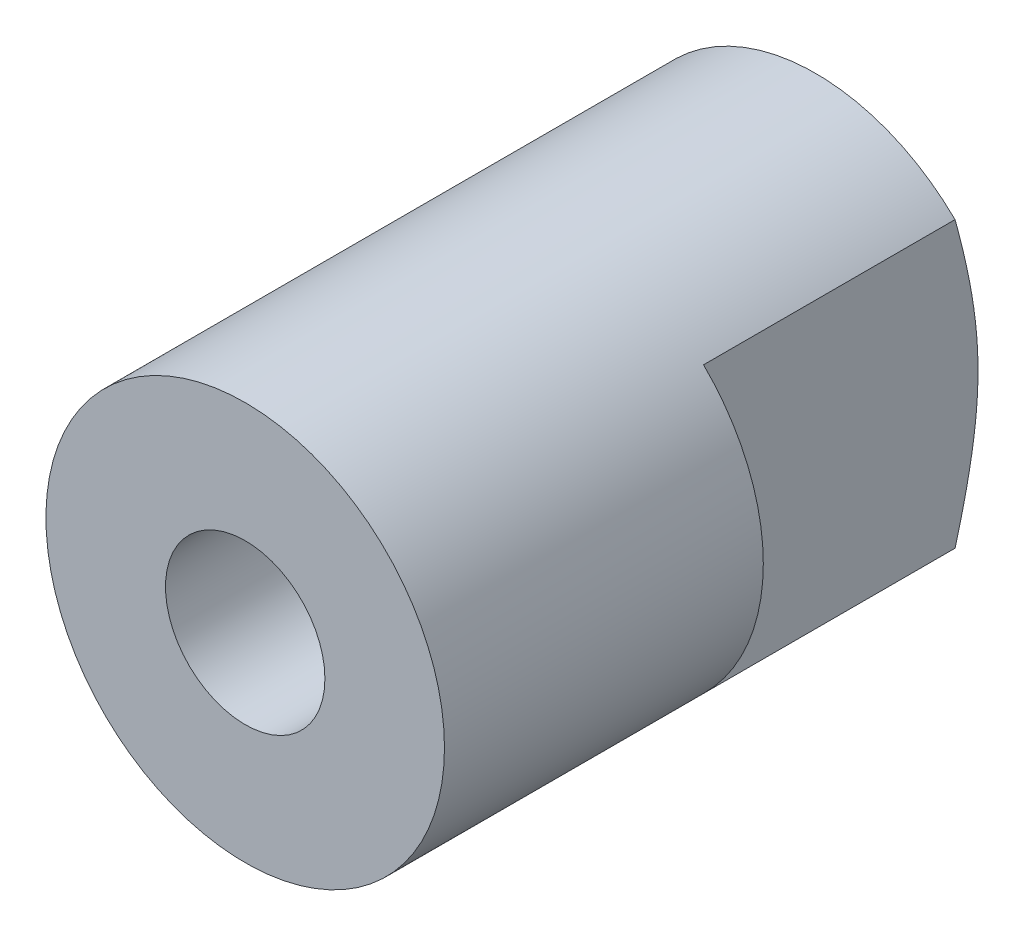
SolidWorks part; units mm, degrees
ref_plane "Front Plane" through (0, 0, 0) normal (0, 0, 1) x (1, 0, 0)
ref_plane "Top Plane" through (0, 0, 0) normal (0, 1, 0) x (1, 0, 0)
ref_plane "Right Plane" through (0, 0, 0) normal (1, 0, 0) x (0, 0, -1)
sketch "Sketch1" plane through (0, 0, 0) normal (0, 0, 1) x (1, 0, 0)
  circle A0 centre (0, 0) radius 2.5
  dimension "D1" = 5
extrude "Boss-Extrude1" add sketch "Sketch1" along normal blind 8
cosmetic thread "Cosmetic Thread1" parameters "D2"=4.11
ref_plane "Plane1" through (0, 0, 0.8) normal (0, 0, -1) x (-1, 0, 0)
sketch "Sketch6" plane through (0, 0, 0) normal (0, 0, -1) x (-1, 0, 0)
  circle A0 centre (0, 0) radius 0.25
  dimension "D1" = 0.5
extrude "Cut-Extrude1" cut sketch "Sketch6" against normal blind 1
chamfer "Chamfer1" distance 2.2 angle 21 1 edges at (2.5, 0, 0) first distance on face at (-0.25, 0, 0)
sketch "Sketch7" plane through (0, 0, 0) normal (0, 1, 0) x (1, 0, 0)
  line L1 (1.75, 1.0072) -> (3.4383, 1.0072)
  line L2 (1.75, 1.0072) -> (1.75, -4)
  line L3 (1.75, -4) -> (3.4383, -4)
  line L4 (3.4383, 1.0072) -> (3.4383, -4)
  dimension "D1" = 1.75
  dimension "D2" = 4
extrude "Cut-Extrude2" cut sketch "Sketch7" against normal blind 5 and the other way blind 5
mirror "Mirror1" about plane through (0, 0, 0) normal (1, 0, 0) of "Cut-Extrude2"
hole_wizard "Ø2.0 (2) Diameter Hole1" positions "Sketch9" profile "Sketch8" hole size "Ø2.0" standard "Ansi Metric"
sketch "Sketch9" plane through (0, 0, 8) normal (0, 0, 1) x (1, 0, 0)
  point P0 (0, 0)
sketch "Sketch8" plane through (0, 0, 8) normal (1, 0, 0) x (0, -1, 0)
  line L0 (0, 0) -> (0, 7.6509)
  line L1 (0, 7.6509) -> (1, 7.05)
  line L2 (1, 7.05) -> (1, 0)
  line L5 (1, 0) -> (0, 0)
  line L10 (0, 7.6509) -> (-1, 7.05) construction
  line L11 (0, -6.35) -> (0, 107.95) construction
  dimension "Hole Dia." = 2
  dimension "Hole Depth" = 7.05
  dimension "Drill Angle" = 118
